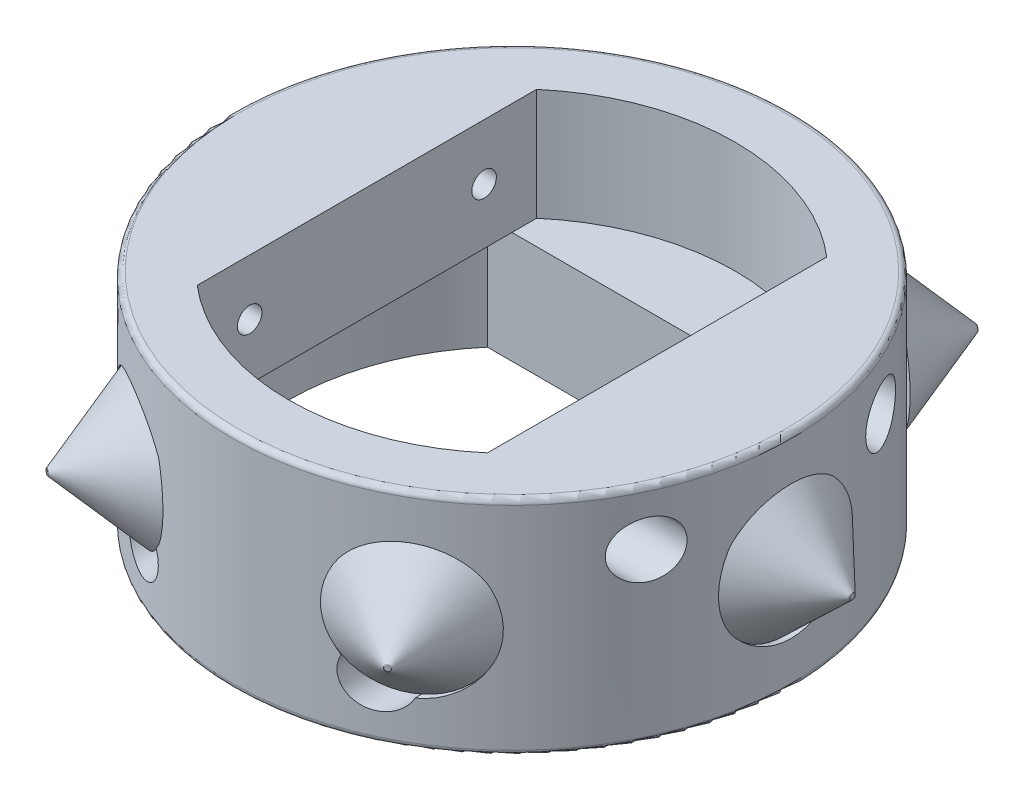
SolidWorks part; units mm, degrees
material "ABS"
ref_plane "正面" through (0, 0, 0) normal (0, 0, 1) x (1, 0, 0)
ref_plane "平面" through (0, 0, 0) normal (0, 1, 0) x (1, 0, 0)
ref_plane "右側面" through (0, 0, 0) normal (1, 0, 0) x (0, 0, -1)
sketch "ｽｹｯﾁ1" plane through (0, 0, 0) normal (0, 1, 0) x (1, 0, 0)
  circle A0 centre (0, 0) radius 25
  circle A1 centre (0, 0) radius 20
  dimension "D1" = 40
  dimension "D2" = 50
extrude "ﾎﾞｽ - 押し出し1" add sketch "ｽｹｯﾁ1" along normal blind 10 and the other way blind 10
fillet "ﾌｨﾚｯﾄ1" radius 0.5 2 edges at (0, -10, 25) (0, 10, 25)
sketch "ｽｹｯﾁ2" plane through (0, 0, 0) normal (0, 0, 1) x (1, 0, 0)
  line L0 (30.4692, 0.2795) -> (24.5, 6)
  line L1 (24.5, 6) -> (24.5, 0)
  line L2 (24.5, 0) -> (30.5, 0) construction
  line L4 (-25, 9.5) -> (25, 9.5) construction
  line L5 (-25, 9.5) -> (25, 9.5) construction
  line L6 (30.5, 0) -> (24.5, 0)
  line L7 (30.5, 0) -> (30.5, 0.2073)
  arc A0 (30.5, 0.2073) -> (30.4692, 0.2795) centre (30.4, 0.2073) ccw
  point P4 (30.5, 0.25)
  dimension "D5" = 0.1
  dimension "D1" = 0.5
  dimension "D2" = 6
  dimension "D3" = 6
  dimension "D4" = 0.25
revolve "回転1" add sketch "ｽｹｯﾁ2" angle 360 about L6 region at (26.58, 2.0034, 0) other way angle 360
ref_axis "軸1" through (0, -10, 0) along (0, 1, 0)
pattern_circular "円形ﾊﾟﾀｰﾝ5" count 6 over 360 about axis through (0, -10, 0) along (0, 1, 0) of bodies 102
sketch "ｽｹｯﾁ3" plane through (-12.25, 0, 21.2176) normal (0.5, 0, -0.866) x (-0.866, 0, -0.5)
  circle A0 centre (0, 0) radius 4.25
  dimension "D1" = 8.5
extrude "ｶｯﾄ - 押し出し1" cut sketch "ｽｹｯﾁ3" against normal blind 10
pattern_circular "円形ﾊﾟﾀｰﾝ6" count 6 over 360 about axis through (0, -10, 0) along (0, 1, 0) of "ｶｯﾄ - 押し出し1"
sketch "ｽｹｯﾁ4" plane through (0, 0, 0) normal (0, -1, 0) x (1, 0, 0)
  line L0 (-13, 15.1987) -> (-13, -15.1987)
  line L1 (13, 15.1987) -> (13, -15.1987)
  arc A1 (-13, 15.1987) -> (-13, -15.1987) centre (0, 0) ccw
  arc A2 (13, -15.1987) -> (13, 15.1987) centre (0, 0) ccw
  circle A3 centre (0, 0) radius 20 construction
  dimension "D1" = 13
  dimension "D2" = 13
extrude "ﾎﾞｽ - 押し出し2" add sketch "ｽｹｯﾁ4" against normal up to surface (10 mm away) up to face at (0, 10, 24.5)
sketch "ｽｹｯﾁ5" plane through (13, 0, 0) normal (-1, 0, 0) x (0, 0, 1)
  line L0 (15.1987, 5) -> (-15.1987, 5) construction
  line L1 (24.5, 10) -> (-24.5, 10) construction
  line L3 (0, -11) -> (0, 11) construction
  circle A0 centre (10.5, 5) radius 1.1
  circle A1 centre (-10.5, 5) radius 1.1
  dimension "D1" = 2.2
  dimension "D2" = 10.5
  dimension "D3" = 10.5
  dimension "D4" = 5
extrude "ｶｯﾄ - 押し出し2" cut sketch "ｽｹｯﾁ5" against normal through all both and the other way through all
sketch "ｽｹｯﾁ7" plane through (0, 0, 0) normal (0, -1, 0) x (1, 0, 0)
  line L0 (15.1987, -13) -> (-15.1987, -13)
  line L3 (11, 0) -> (-11, 0) construction
  line L4 (15.1987, 13) -> (-15.1987, 13)
  circle A5 centre (0, 0) radius 20 construction
  arc A6 (15.1987, 13) -> (-15.1987, 13) centre (0, 0) ccw
  arc A7 (-15.1987, -13) -> (15.1987, -13) centre (0, 0) ccw
  dimension "D1" = 13
extrude "ﾎﾞｽ - 押し出し7" add sketch "ｽｹｯﾁ7" along normal up to surface (10 mm away) up to face at (0, -10, 24.5)
sketch "ｽｹｯﾁ8" plane through (0, 0, 13) normal (0, 0, -1) x (-1, 0, 0)
  line L0 (0, 0) -> (0, -10) construction
  line L1 (13, 0) -> (-13, 0) construction
  line L2 (-15.1987, -10) -> (15.1987, -10) construction
  line L3 (-15.1987, -5) -> (15.1987, -5) construction
  line L4 (-15.1987, -10) -> (-15.1987, 0) construction
  line L5 (15.1987, -10) -> (15.1987, 0) construction
  circle A1 centre (10.5, -5) radius 1.1
  circle A2 centre (-10.5, -5) radius 1.1
  dimension "D1" = 2.2
  dimension "D2" = 10.5
extrude "ｶｯﾄ - 押し出し3" cut sketch "ｽｹｯﾁ8" against normal through all
sketch "ｽｹｯﾁ9" plane through (-24.5, 0, 0) normal (1, 0, 0) x (0, 0, -1)
  circle A0 centre (0, 0) radius 6 construction
  circle A1 centre (0, 0) radius 6
extrude "ｶｯﾄ - 押し出し4" cut sketch "ｽｹｯﾁ9" against normal through all
pattern_circular "円形ﾊﾟﾀｰﾝ7" count 6 over 360 about axis through (0, -10, 0) along (0, 1, 0) of "ｶｯﾄ - 押し出し4"
ref_plane "平面1" through (0, 0, 25) normal (0, 0, 1) x (1, 0, 0)
sketch "ｽｹｯﾁ11" plane through (0, 0, 25) normal (0, 0, 1) x (1, 0, 0)
  circle A0 centre (10.5, -5) radius 2.5
  circle A1 centre (-10.5, -5) radius 2.5
  arc A2 (11.1734, -5.8698) -> (9.4001, -5.0171) centre (10.5, -5) ccw construction
  arc A3 (-9.4001, -5.0171) -> (-11.1734, -5.8698) centre (-10.5, -5) ccw construction
  dimension "D1" = 5
extrude "ｶｯﾄ - 押し出し5" cut sketch "ｽｹｯﾁ11" against normal blind 8
mirror "ﾐﾗｰ1" about plane through (0, 0, 0) normal (0, 0, 1) of "ｶｯﾄ - 押し出し5"
ref_plane "平面2" through (25, 0, 0) normal (1, 0, 0) x (0, 0, -1)
sketch "ｽｹｯﾁ12" plane through (25, 0, 0) normal (1, 0, 0) x (0, 0, -1)
  circle A0 centre (10.5, 5) radius 2.5
  circle A1 centre (-10.5, 5) radius 2.5
  circle A2 centre (10.5, 5) radius 1.1 construction
  circle A3 centre (-10.5, 5) radius 1.1 construction
  dimension "D1" = 5
extrude "ｶｯﾄ - 押し出し6" cut sketch "ｽｹｯﾁ12" against normal blind 8
mirror "ﾐﾗｰ2" about plane through (0, 0, 0) normal (1, 0, 0) of "ｶｯﾄ - 押し出し6"
